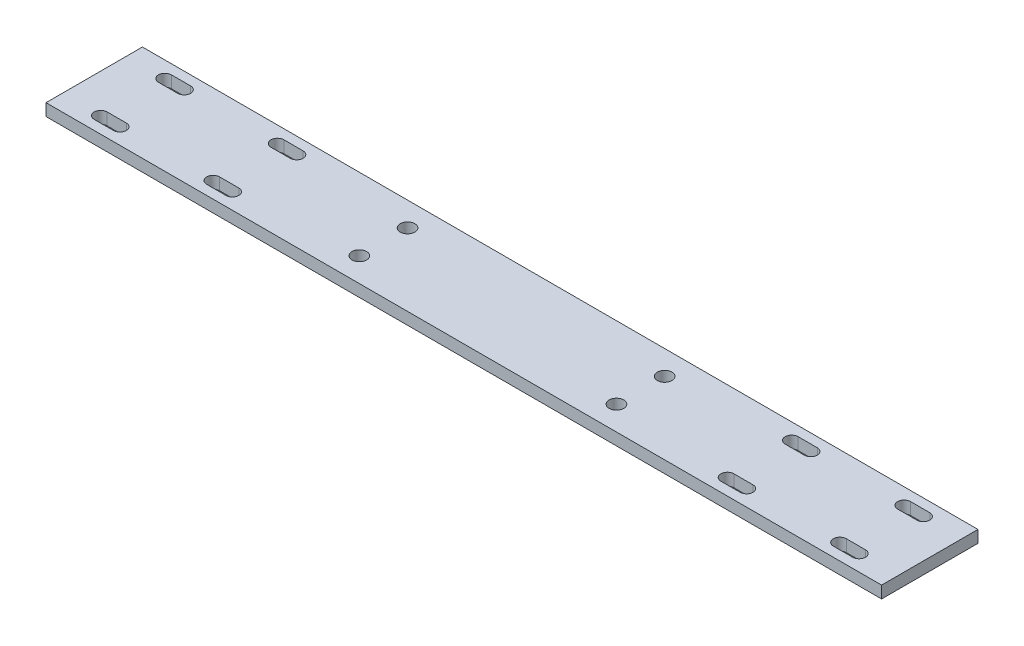
SolidWorks part; units mm, degrees
material "6061 Alloy"
ref_plane "Front Plane" through (0, 0, 0) normal (0, 0, 1) x (1, 0, 0)
ref_plane "Top Plane" through (0, 0, 0) normal (0, 1, 0) x (1, 0, 0)
ref_plane "Right Plane" through (0, 0, 0) normal (1, 0, 0) x (0, 0, -1)
sketch "Sketch1" plane through (0, 0, 0) normal (0, 1, 0) x (1, 0, 0)
  line L1 (165.1, -19.05) -> (-165.1, -19.05)
  line L2 (165.1, -19.05) -> (165.1, 19.05)
  line L3 (165.1, 19.05) -> (-165.1, 19.05)
  line L4 (-165.1, -19.05) -> (-165.1, 19.05)
  line L5 (165.1, -19.05) -> (-165.1, 19.05) construction
  line L6 (165.1, 19.05) -> (-165.1, -19.05) construction
  point P0 (0, 0)
  dimension "D1" = 330.2
  dimension "D2" = 38.1
extrude "Boss-Extrude1" add sketch "Sketch1" along normal mid plane 4.7625
hole_wizard "#10 Clearance Slot1" positions "Sketch2" profile "Sketch3" size "#10" standard "ANSI Inch" slot yes end condition through all
sketch "Sketch2" plane through (0, 2.3813, 0) normal (0, 1, 0) x (1, 0, 0)
  line L0 (-152.4, -12.7) -> (-139.7, -12.7) construction
  line L1 (0, -1000) -> (0, 49000) construction
  line L2 (-1000, 0) -> (49000, 0) construction
  line L3 (-123.825, -992.6448) -> (-123.825, 49007.3552) construction
  point P0 (-146.05, -12.7)
  point P17 (-101.6, -12.7)
  point P18 (-101.6, 12.7)
  point P19 (-146.05, 12.7)
  point P20 (101.6, 12.7)
  point P21 (101.6, -12.7)
  point P22 (146.05, -12.7)
  point P23 (146.05, 12.7)
  dimension "D1" = 12.7
  dimension "D2" = 12.7
  dimension "D3" = 123.825
  dimension "D4" = 22.225
sketch "Sketch3" plane through (-146.05, 2.3813, 12.7) normal (1, 0, 0) x (0, 0, 1)
  line L0 (0, 0) -> (0, 4.7625)
  line L1 (0, 4.7625) -> (2.5527, 4.7625)
  line L2 (2.5527, 4.7625) -> (2.5527, 0)
  line L5 (2.5527, 0) -> (0, 0)
  line L11 (0, -6.35) -> (0, 107.95) construction
  dimension "Thru Hole Dia." = 5.1054
  dimension "Thru Hole Depth" = 4.7625
hole_wizard "1/4-20 Tapped Hole1" positions "Sketch4" profile "Sketch5" tap size "1/4-20" standard "ANSI Inch" end condition through all
sketch "Sketch4" plane through (0, 2.3813, 0) normal (0, 1, 0) x (1, 0, 0)
  line L0 (-1000, 0) -> (49000, 0) construction
  line L1 (0, -1000) -> (0, 49000) construction
  point P0 (-50.8, 9.525)
  point P2 (-50.8, -9.525)
  point P14 (50.8, -9.525)
  point P15 (50.8, 9.525)
  dimension "D1" = 19.05
  dimension "D2" = 50.8
sketch "Sketch5" plane through (-50.8, 2.3813, -9.525) normal (1, 0, 0) x (0, 0, 1)
  line L0 (0, 0) -> (0, 4.7625)
  line L1 (0, 4.7625) -> (2.8956, 4.7625)
  line L2 (2.8956, 4.7625) -> (2.8956, 0)
  line L5 (2.8956, 0) -> (0, 0)
  line L11 (0, -6.35) -> (0, 107.95) construction
  dimension "Thru Tap Drill Dia." = 5.7912
  dimension "Thru Tap Drill Depth" = 4.7625
cosmetic thread "Hole Thread1"
cosmetic thread "Hole Thread2"
cosmetic thread "Hole Thread3"
cosmetic thread "Hole Thread4"
